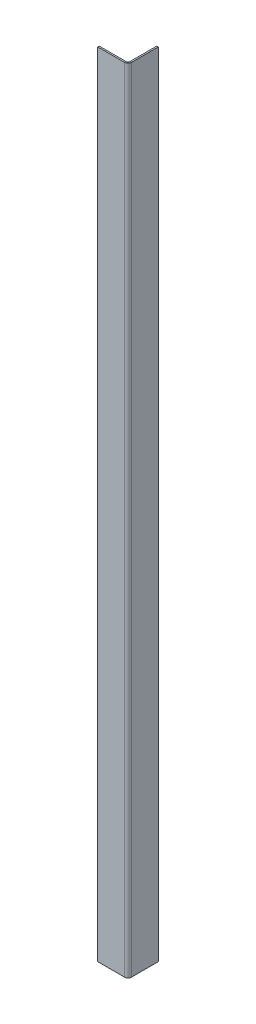
SolidWorks part; units mm, degrees
note: The reader was unsure of these and kept them because the rebuilt part matched: flange length of "Edge-Flange1".
material "Galvanized Steel"
ref_plane "Front" through (0, 0, 0) normal (0, 0, 1) x (1, 0, 0)
ref_plane "Top" through (0, 0, 0) normal (0, 1, 0) x (1, 0, 0)
ref_plane "Right" through (0, 0, 0) normal (1, 0, 0) x (0, 0, -1)
sketch "Sketch1" plane through (0, 0, 0) normal (1, 0, 0) x (0, 0, -1)
  line L1 (20, -522.5) -> (-20, -522.5)
  line L2 (20, -522.5) -> (20, 522.5)
  line L3 (20, 522.5) -> (-20, 522.5)
  line L4 (-20, -522.5) -> (-20, 522.5)
  line L5 (20, -522.5) -> (-20, 522.5) construction
  line L6 (20, 522.5) -> (-20, -522.5) construction
  point P0 (0, 0)
  dimension "D1" = 40
  dimension "D2" = 1045
base flange "Base-Flange1" sketch "Sketch1" thickness 2 reverse thickness direction no parameters "D1"=13
edge flange "Edge-Flange1" sketch "Sketch8" flange angle 90 flange length 40 flange position material inside bend radius 2.5 thickness 2 relief rectangular parameters "D6"=10
sketch "Sketch8" plane through (-2, 0, 20) normal (0, 0, -1) x (0, -1, 0)
  line L2 (-522.5, 0) -> (-522.5, 38)
  line L3 (-522.5, 38) -> (522.5, 38)
  line L4 (522.5, 38) -> (522.5, 0)
  line L5 (522.5, 0) -> (-522.5, 0) construction
  line L6 (522.5, 0) -> (-522.5, 0)
bend "EdgeBend1" bend radius 2.5 bend angle 90 parameters "D5"=1
sketch "Bend-Lines1" [suppressed] plane through (0, 0, 0) normal (0, 1, 0) x (1, 0, 0)
sketch "Bounding-Box1" [suppressed] plane through (0, 0, 0) normal (0, 1, 0) x (1, 0, 0)
sheet metal parameters "Sheet-Metal1" thickness 2 parameters "D1"=13
flat pattern "Flat-Pattern1" [suppressed]
sketch "Bend-Lines2" plane through (0, 0, 0) normal (0, 1, 0) x (1, 0, 0)
sketch3d "Bounding-Box2" [suppressed]
  line L0 (-20, 1500, 0) -> (-20, -1500, 0) construction
  line L1 (20, 1500, 0) -> (20, -1500, 0) construction
  line L2 (-20, 1500, 0) -> (20, 1500, 0) construction
  line L3 (-20, -1500, 0) -> (20, -1500, 0) construction
sheet metal parameters "Sheet-Metal2" thickness 2 parameters "D1"=13
flat pattern "Flat-Pattern1"
sketch "Bend-Lines2" plane through (0, 0, 0) normal (1, 0, 0) x (0, 0, -1)
  line L0 (-18.2489, 522.5) -> (-18.2489, -522.5) construction
  line L1 (-18.2489, 522.5) -> (-18.2489, -522.5) construction
sketch3d "Bounding-Box2" [suppressed]
  line L0 (20, 522.5, 0) -> (20, -522.5, 0) construction
  line L1 (-56.4978, 522.5, 0) -> (-56.4978, -522.5, 0) construction
  line L2 (20, 522.5, 0) -> (-56.4978, 522.5, 0) construction
  line L3 (20, -522.5, 0) -> (-56.4978, -522.5, 0) construction
bend of the flat pattern "Flatten-<EdgeBend1>1"
